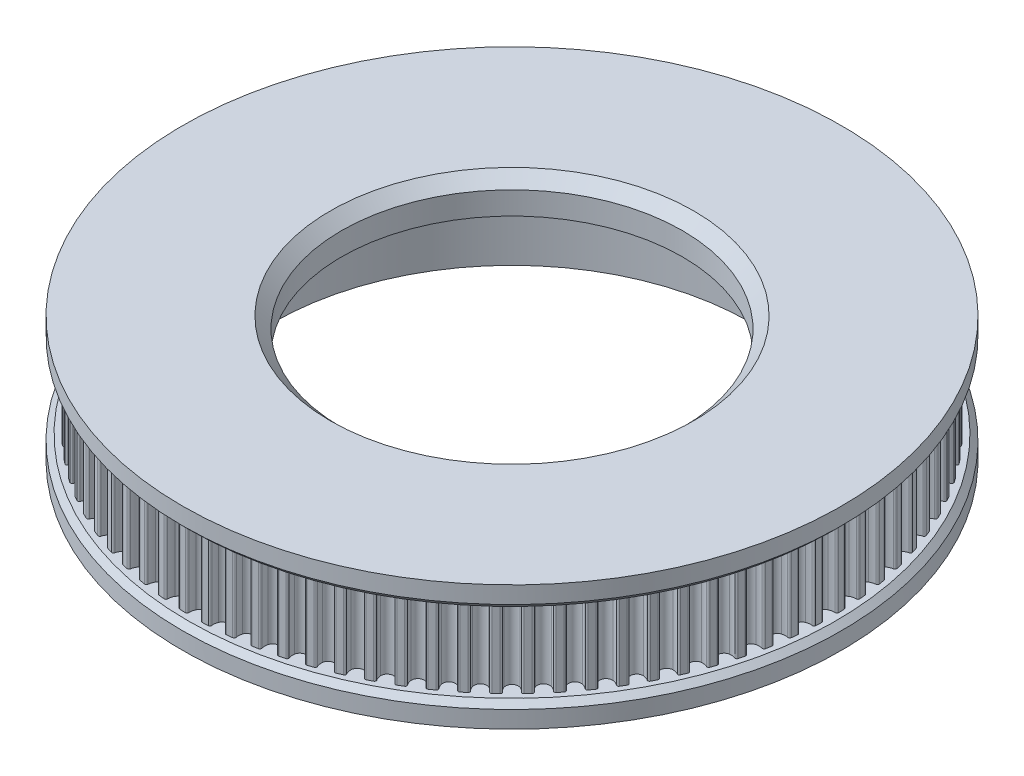
SolidWorks part; units mm, degrees
ref_plane "Płaszczyzna przednia" through (0, 0, 0) normal (0, 0, 1) x (1, 0, 0)
ref_plane "Płaszczyzna górna" through (0, 0, 0) normal (0, 1, 0) x (1, 0, 0)
ref_plane "Płaszczyzna prawa" through (0, 0, 0) normal (1, 0, 0) x (0, 0, -1)
sketch "Sketch1" plane through (0, 0, 0) normal (0, 1, 0) x (1, 0, 0)
  circle A0 centre (0, 0) radius 24 construction
  circle A1 centre (0, 0) radius 28.01
  dimension "D1" = 48
  dimension "D2" = 56.02
extrude "Boss-Extrude1" add sketch "Sketch1" along normal blind 11
sketch "Sketch8" plane through (0, 11, 0) normal (0, 1, 0) x (1, 0, 0)
  line L0 (0, 0) -> (0, 46.5402)
  circle A0 centre (0, 0) radius 28.01
  circle A1 centre (0, 0) radius 27.755 construction
  circle A2 centre (0, 27.56) radius 0.555
  circle A3 centre (-0.4014, 27.7521) radius 1
  circle A4 centre (0.4014, 27.7521) radius 1
  circle A6 centre (-0.7444, 27.8501) radius 0.15
  circle A7 centre (0.7444, 27.8501) radius 0.15
  point P6 (0, 27.755)
  dimension "D1" = 55.51
  dimension "D2" = 1.11
  dimension "D4" = 2
  dimension "D5" = 0.3
  dimension "D6" = 56.02
  dimension "D3" = 0.195
extrude "Cut-Extrude1" cut sketch "Sketch8" against normal blind 7 from offset 2 offset against normal yes
pattern_circular "CirPattern1" count 88 over 360 about axis through (0, 0, 0) along (0, 1, 0) of "Cut-Extrude1"
sketch "Sketch10" plane through (0, 11, 0) normal (0, 1, 0) x (1, 0, 0)
  circle A0 centre (0, 0) radius 28.01 construction
  circle A1 centre (0, 0) radius 28.01
  circle A2 centre (0, 0) radius 29
  dimension "D1" = 58
extrude "Boss-Extrude2" add sketch "Sketch10" against normal up to surface (2 mm away)
sketch "Sketch11" plane through (0, 0, 0) normal (0, -1, 0) x (1, 0, 0)
  circle A0 centre (0, 0) radius 29
  circle A1 centre (0, 0) radius 25.8
  dimension "D1" = 58
extrude "Boss-Extrude3" add sketch "Sketch11" against normal up to surface (2 mm away)
chamfer "Chamfer1" distance 0.5 angle 45 2 edges at (0, 2, 29) (0, 9, 29)
sketch "Sketch12" plane through (0, 0, 0) normal (0, -1, 0) x (1, 0, 0)
  circle A0 centre (0, 0) radius 21
  dimension "D1" = 42
extrude "Cut-Extrude2" cut sketch "Sketch12" against normal blind 8
sketch "Sketch13" plane through (0, 8, 0) normal (0, -1, 0) x (1, 0, 0)
  circle A0 centre (0, 0) radius 15
  circle A1 centre (0, 0) radius 21
  circle A2 centre (0, 0) radius 21 construction
  dimension "D1" = 0
  dimension "D2" = 6
extrude "Cut-Extrude3" cut sketch "Sketch13" against normal through all
chamfer "Chamfer2" distance 1 angle 45 1 edges at (0, 11, -15)
